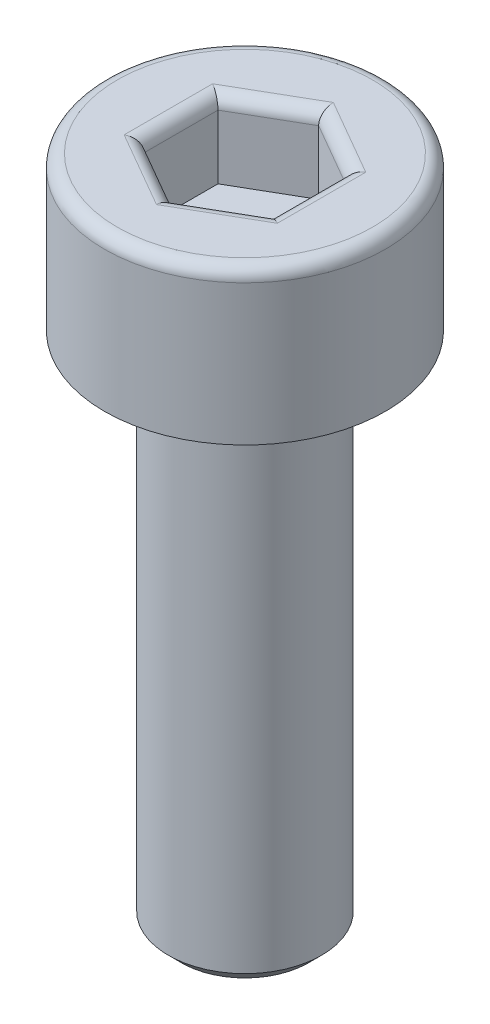
SolidWorks part; units mm, degrees
material "Ductile Iron"
ref_plane "Plano frontal" through (0, 0, 0) normal (0, 0, 1) x (1, 0, 0)
ref_plane "Plano superior" through (0, 0, 0) normal (0, 1, 0) x (1, 0, 0)
ref_plane "Plano direito" through (0, 0, 0) normal (1, 0, 0) x (0, 0, -1)
sketch "Esboço1" plane through (0, 0, 0) normal (0, 1, 0) x (1, 0, 0)
  circle A0 centre (0, 0) radius 2.75
  dimension "D1" = 5.5
extrude "Ressalto-extrusão1" add sketch "Esboço1" along normal blind 3
sketch "Esboço2" plane through (0, 3, 0) normal (0, 1, 0) x (1, 0, 0)
  line L0 (0, -1.4434) -> (1.25, -0.7217)
  line L1 (0, 1.4434) -> (-1.25, 0.7217)
  line L2 (-1.25, 0.7217) -> (-1.25, -0.7217)
  line L3 (-1.25, -0.7217) -> (0, -1.4434)
  line L4 (1.25, -0.7217) -> (1.25, 0.7217)
  line L5 (1.25, 0.7217) -> (0, 1.4434)
  circle A0 centre (0, 0) radius 1.25 construction
  dimension "D1" = 2.5
extrude "Corte-extrusão1" cut sketch "Esboço2" against normal blind 1.5
fillet "Filete2" radius 0.25 7 edges at (0, 3, 2.75) (-0.625, 3, -1.0825) (-1.25, 3, 0) (-0.625, 3, 1.0825) (0.625, 3, 1.0825) (1.25, 3, 0) (0.625, 3, -1.0825)
sketch "Esboço10" plane through (0, 0, 0) normal (0, -1, 0) x (1, 0, 0)
  circle A0 centre (0, 0) radius 2.75
extrude "Ressalto-extrusão2" add sketch "Esboço10" against normal blind 0.75
sketch "Esboço11" plane through (0, 0, 0) normal (0, -1, 0) x (1, 0, 0)
  circle A0 centre (0, 0) radius 2.25
  dimension "D1" = 4.5
extrude "Ressalto-extrusão3" add sketch "Esboço11" along normal blind 0.1
fillet "Filete3" radius 0.35 1 edges at (0, -0.1, -2.25)
sketch "Esboço12" plane through (0, -0.1, 0) normal (0, -1, 0) x (1, 0, 0)
  circle A0 centre (0, 0) radius 1.5
  dimension "D1" = 3
extrude "Ressalto-extrusão4" add sketch "Esboço12" along normal blind 10
chamfer "Chanfro4" distance 0.25 angle 45 1 edges at (0, -10.1, -1.5)
sketch "Esboço17" plane through (0, -10.1, 0) normal (0, -1, 0) x (1, 0, 0)
  circle A0 centre (0, 0) radius 1.5
  dimension "D1" = 3
